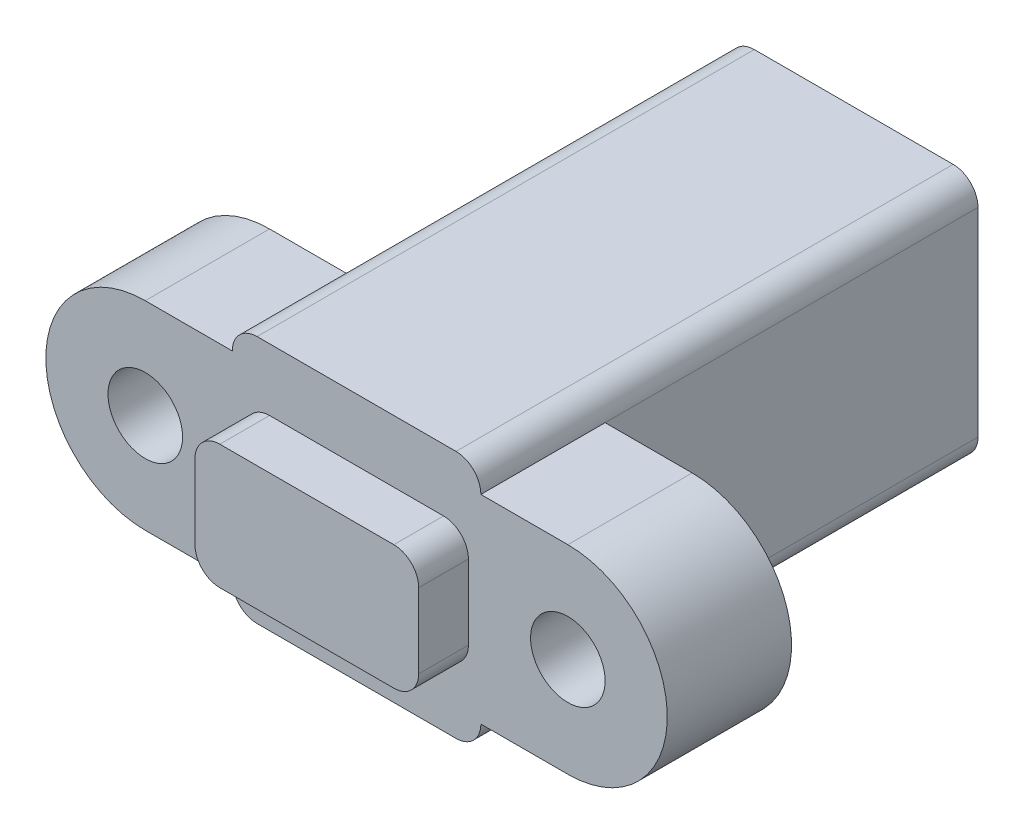
SolidWorks part; units mm, degrees
ref_plane "Front Plane" through (0, 0, 0) normal (0, 0, 1) x (1, 0, 0)
ref_plane "Top Plane" through (0, 0, 0) normal (0, 1, 0) x (1, 0, 0)
ref_plane "Right Plane" through (0, 0, 0) normal (1, 0, 0) x (0, 0, -1)
sketch "Sketch2" plane through (0, 0, 0) normal (0, 0, 1) x (1, 0, 0)
  line L0 (0, 0) -> (-17, 0) construction
  line L1 (0, -4) -> (-17, -4)
  line L2 (0, 4) -> (-17, 4)
  line L4 (-12.5, 5) -> (-4.5, 5)
  line L5 (-13.5, 4) -> (-13.5, -4)
  line L6 (-12.5, -5) -> (-4.5, -5)
  line L7 (-3.5, 4) -> (-3.5, -4)
  arc A0 (0, -4) -> (0, 4) centre (0, 0) ccw
  arc A1 (-17, 4) -> (-17, -4) centre (-17, 0) ccw
  circle A2 centre (-17, 0) radius 1.5
  circle A3 centre (0, 0) radius 1.5
  arc A4 (-4.5, -5) -> (-3.5, -4) centre (-4.5, -4) ccw
  arc A5 (-4.5, 5) -> (-3.5, 4) centre (-4.5, 4) cw
  arc A6 (-12.5, 5) -> (-13.5, 4) centre (-12.5, 4) ccw
  arc A7 (-13.5, -4) -> (-12.5, -5) centre (-12.5, -4) ccw
  point P3 (-8.5, 0)
  point P16 (-8.5, 5)
  point P17 (-13.5, 0)
  point P22 (-3.5, 5)
  point P25 (-13.5, 5)
  point P28 (-13.5, -5)
  dimension "D3" = 3
  dimension "D4" = 3
  dimension "D7" = 1
  dimension "D8" = 1
  dimension "D9" = 1
  dimension "D10" = 1
  dimension "D1" = 17
  dimension "D2" = 8
  dimension "D5" = 10
  dimension "D6" = 10
extrude "Boss-Extrude1" add sketch "Sketch2" along normal blind 5 contours L2 A1 L1 L5 A2 | L7 L0 L5 L1 | L4 A6 L2 A5 | L0 L7 L2 L5 | L1 A7 L6 A4 | A3 L7 L1 A0 L2 region at (-3.3903, 2, 0) region at (-8.5, -2, 0) region at (-8.5, 2, 0) region at (-13.6097, -2, 0) region at (-8.5, 4.4876, 0) region at (-8.5, -4.4876, 0)
sketch "Sketch3" plane through (0, 0, 5) normal (0, 0, 1) x (1, 0, 0)
  line L0 (-13.5, 4) -> (-3.5, -4) construction
  line L2 (-12, -2.5) -> (-5, -2.5)
  line L3 (-13, -1.5) -> (-13, 1.5)
  line L4 (-12, 2.5) -> (-5, 2.5)
  line L5 (-4, -1.5) -> (-4, 1.5)
  line L6 (-13, -2.5) -> (-4, 2.5) construction
  line L7 (-13, 2.5) -> (-4, -2.5) construction
  arc A0 (-5, 2.5) -> (-4, 1.5) centre (-5, 1.5) cw
  arc A1 (-5, -2.5) -> (-4, -1.5) centre (-5, -1.5) ccw
  arc A2 (-12, -2.5) -> (-13, -1.5) centre (-12, -1.5) cw
  arc A3 (-13, 1.5) -> (-12, 2.5) centre (-12, 1.5) cw
  point P4 (-8.5, 0)
  dimension "D3" = 1
  dimension "D4" = 1
  dimension "D5" = 1
  dimension "D6" = 1
  dimension "D1" = 9
  dimension "D2" = 5
extrude "Boss-Extrude2" add sketch "Sketch3" along normal blind 2
extrude "Boss-Extrude3" add sketch "Sketch2<3>" against normal blind 15 contours L4 A6 L2 A5 | L0 L7 L2 L5 | L7 L0 L5 L1 | L1 A7 L6 A4 region at (-8.5, -2, 0) region at (-8.5, 2, 0) region at (-8.5, 4.4876, 0) region at (-8.5, -4.4876, 0)
sketch "Sketch2<3>" plane through (0, 0, 0) normal (0, 0, 1) x (1, 0, 0) same geometry as "Sketch2"
